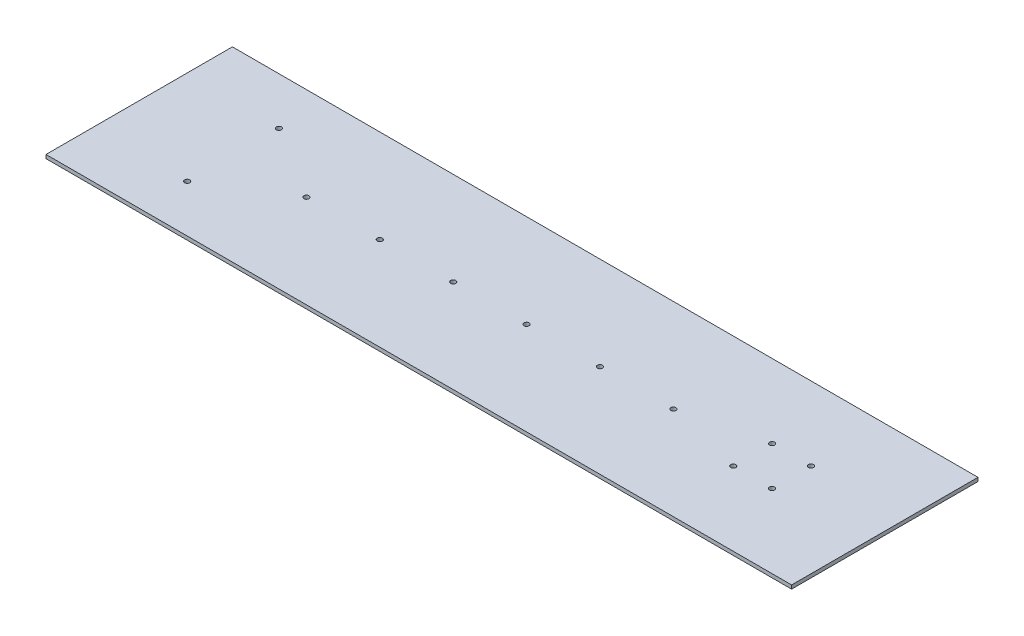
SolidWorks part; units mm, degrees
ref_plane "Front Plane" through (0, 0, 0) normal (0, 0, 1) x (1, 0, 0)
ref_plane "Top Plane" through (0, 0, 0) normal (0, 1, 0) x (1, 0, 0)
ref_plane "Right Plane" through (0, 0, 0) normal (1, 0, 0) x (0, 0, -1)
sketch "Sketch1" plane through (0, 0, 0) normal (0, 1, 0) x (1, 0, 0)
  line L1 (-304.8, 76.2) -> (304.8, 76.2)
  line L2 (-304.8, 76.2) -> (-304.8, -76.2)
  line L3 (-304.8, -76.2) -> (304.8, -76.2)
  line L4 (304.8, 76.2) -> (304.8, -76.2)
  point P4 (0, 76.2)
  point P6 (304.8, 0)
  dimension "D1" = 609.6
  dimension "D2" = 152.4
extrude "Boss-Extrude1" add sketch "Sketch1" along normal blind 3
hole_wizard "M5x0.8 Tapped Hole1" positions "Sketch2" profile "Sketch4" tap size "M5x0.8" standard "ANSI Metric" end condition through all
sketch "Sketch2" plane through (0, 3, 0) normal (0, 1, 0) x (1, 0, 0)
  point P0 (228.5432, -15.875)
  point P3 (196.7932, -15.875)
  point P6 (196.7932, 15.875)
  point P9 (228.5432, 15.875)
  point P11 (131.9318, 0)
  point P14 (71.9318, 0)
  point P17 (11.9318, 0)
  point P20 (-48.0682, 0)
  point P23 (-108.0682, 0)
  point P26 (-168.0682, 0)
  point P29 (-228.0682, -37.5)
  point P32 (-228.0682, 37.5)
  point P36 (0, 0)
  point P37 (228.5432, 15.875)
sketch "Sketch4" plane through (228.5432, 3, 15.875) normal (1, 0, 0) x (0, 0, 1)
  line L0 (0, 0) -> (0, 3)
  line L1 (0, 3) -> (2.1, 3)
  line L2 (2.1, 3) -> (2.1, 0)
  line L5 (2.1, 0) -> (0, 0)
  line L11 (0, -6.35) -> (0, 107.95) construction
  dimension "Thru Tap Drill Dia." = 4.2
  dimension "Thru Tap Drill Depth" = 3
